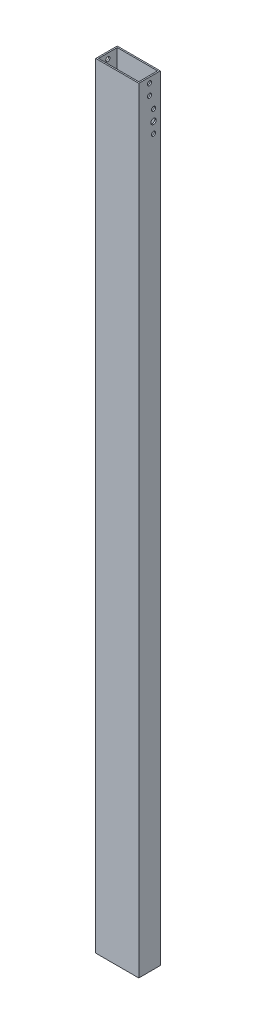
SolidWorks part; units mm, degrees
material "6061-T6 (SS)"
ref_plane "Front Plane" through (0, 0, 0) normal (0, 0, 1) x (1, 0, 0)
ref_plane "Top Plane" through (0, 0, 0) normal (0, 1, 0) x (1, 0, 0)
ref_plane "Right Plane" through (0, 0, 0) normal (1, 0, 0) x (0, 0, -1)
sketch "Sketch1" plane through (0, 0, 0) normal (0, 0, 1) x (1, 0, 0)
  line L1 (-25.4, -457.2) -> (25.4, -457.2)
  line L2 (-25.4, -457.2) -> (-25.4, 457.2)
  line L3 (-25.4, 457.2) -> (25.4, 457.2)
  line L4 (25.4, -457.2) -> (25.4, 457.2)
  line L5 (-25.4, -457.2) -> (25.4, 457.2) construction
  line L6 (-25.4, 457.2) -> (25.4, -457.2) construction
  point P0 (0, 0)
  dimension "D1" = 50.8
  dimension "D2" = 914.4
extrude "Boss-Extrude1" add sketch "Sketch1" along normal mid plane 25.4
shell "Shell1" thickness 1.5875 removed face at (0, -457.2, 0) removed face at (0, 457.2, 0)
sketch "Sketch3" plane through (0, 0, 0) normal (1, 0, 0) x (0, 0, -1)
  line L0 (-12.7, -457.2) -> (12.7, -457.2) construction
  line L1 (-12.7, 457.2) -> (12.7, 457.2) construction
  circle A0 centre (0, 438.15) radius 2.4892
  circle A1 centre (0, 450.85) radius 2.4892
  point P6 (0, -457.2)
  point P7 (0, 438.3423)
  dimension "D1" = 4.9784
  dimension "D2" = 6.35
  dimension "D3" = 12.7
extrude "Cut-Extrude1" cut sketch "Sketch3" against normal through all both and the other way through all
sketch "Sketch4" plane through (0, 0, 0) normal (1, 0, 0) x (0, 0, -1)
  line L0 (12.7, 457.2) -> (12.7, -457.2) construction
  line L3 (-12.7, 457.2) -> (12.7, 457.2) construction
  circle A0 centre (4.7625, 409.575) radius 3.175
  circle A1 centre (4.7625, 422.275) radius 2.4892
  circle A2 centre (4.7625, 396.875) radius 2.4892
  dimension "D1" = 6.35
  dimension "D4" = 4.9784
  dimension "D2" = 7.9375
  dimension "D5" = 12.7
  dimension "D6" = 12.7
  dimension "D3" = 47.625
extrude "Cut-Extrude2" cut sketch "Sketch4" against normal through all both and the other way through all
sketch "Sketch5" plane through (0, 0, 0) normal (0, 0, 1) x (1, 0, 0)
  line L1 (-15.875, 423.0688) -> (15.875, 423.0688)
  line L2 (-15.875, 423.0688) -> (-15.875, 396.0813)
  line L3 (-15.875, 396.0813) -> (15.875, 396.0813)
  line L4 (15.875, 423.0688) -> (15.875, 396.0813)
  line L6 (25.4, 457.2) -> (-25.4, 457.2) construction
  point P4 (-15.875, 409.575)
  point P8 (0, 423.0688)
  point P9 (0, 457.2)
  dimension "D1" = 31.75
  dimension "D2" = 26.9875
  dimension "D3" = 47.625
extrude "Cut-Extrude3" cut sketch "Sketch5" against normal through all
fillet "Fillet1" radius 3.175 4 edges at (15.875, 423.0688, -11.9062) (15.875, 396.0813, -11.9062) (-15.875, 396.0813, -11.9062) (-15.875, 423.0688, -11.9062)
equation "\"D6@Sketch4\"=\"D5@Sketch4\""
